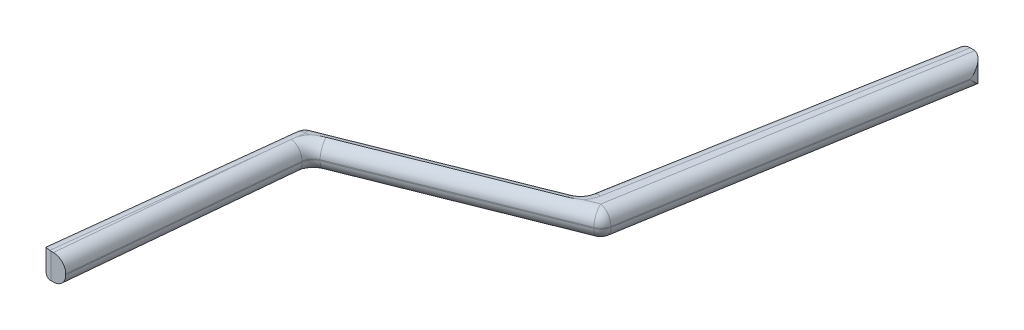
SolidWorks part; units mm, degrees
ref_plane "Plano frontal" through (0, 0, 0) normal (0, 0, 1) x (1, 0, 0)
ref_plane "Plano superior" through (0, 0, 0) normal (0, 1, 0) x (1, 0, 0)
ref_plane "Plano direito" through (0, 0, 0) normal (1, 0, 0) x (0, 0, -1)
sketch "Esboço1" plane through (0, 0, 0) normal (0, 1, 0) x (1, 0, 0)
  line L0 (0.0211, 6.7) -> (0, 6.7)
  line L1 (-2.7, 0) -> (-3, 0)
  line L2 (-3, 0) -> (-2.7135, 2.5062)
  line L3 (-2.7135, 2.5062) -> (-0.604, 3.35)
  line L4 (-0.604, 3.35) -> (0, 6.7)
  line L5 (-3, 0) -> (-2.7, 0)
  line L6 (-2.7, 0) -> (-2.4753, 2.3531)
  line L7 (-2.4753, 2.3531) -> (-0.5183, 3.1359)
  line L8 (-0.5183, 3.1359) -> (-0.2725, 3.2342)
  line L9 (-0.2725, 3.2342) -> (0.3147, 6.7)
  line L10 (0.3147, 6.7) -> (0.0211, 6.7)
  dimension "D3" = 0.3
extrude "Ressalto-extrusão1" add sketch "Esboço1" along normal blind 0.27 contours L9 L10 L0 L4 L3 L2 L1 L6 L7 L8
fillet "Filete2" radius 0.13 19 edges at (-2.5876, 0.27, -1.1766) (-2.5876, 0, -1.1766) (-1.6587, 0.27, -2.9281) (-1.6587, 0, -2.9281) (-2.7135, 0.135, -2.5062) (-2.8567, 0.27, -1.2531) (-3, 0.135, 0) (-2.8567, 0, -1.2531) (0, 0.135, -6.7) (-0.302, 0.27, -5.025) (-0.604, 0.135, -3.35) (-0.302, 0, -5.025) (0.0211, 0.27, -4.9671) (0.3147, 0.135, -6.7) (0.0211, 0, -4.9671) (-2.4753, 0.135, -2.3531) (-1.3739, 0.27, -2.7937) (-0.2725, 0.135, -3.2342) (-1.3739, 0, -2.7937)
